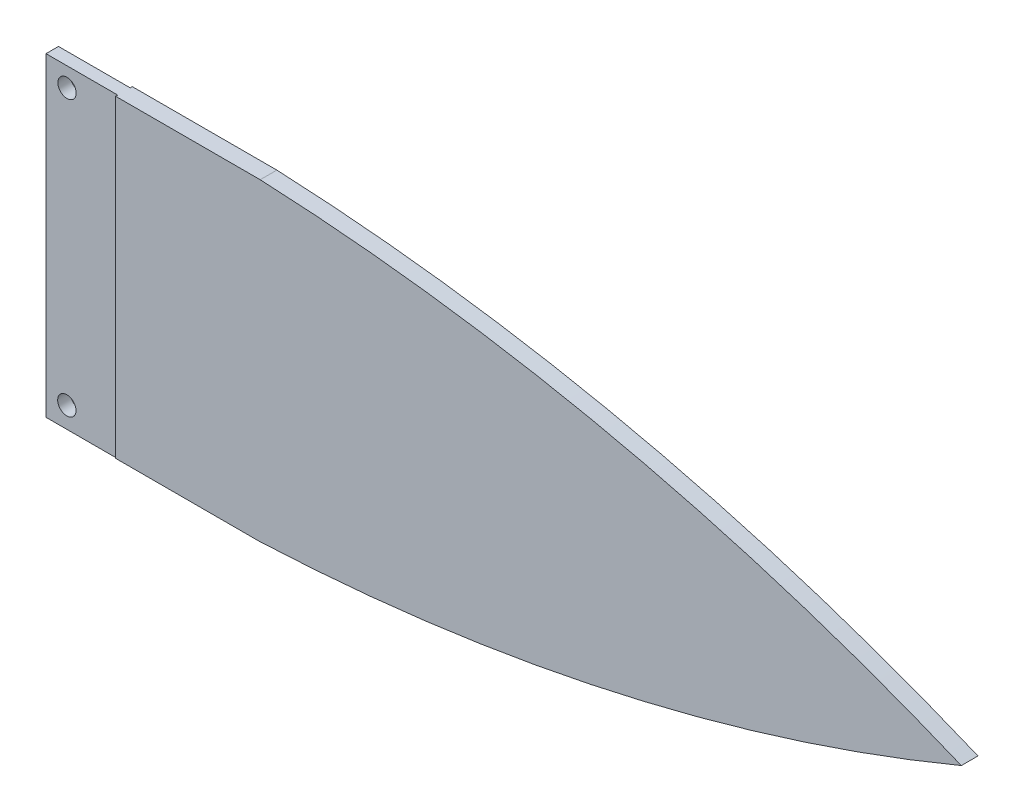
SolidWorks part; units mm, degrees
ref_plane "前基準面" through (0, 0, 0) normal (0, 0, 1) x (1, 0, 0)
ref_plane "上基準面" through (0, 0, 0) normal (0, 1, 0) x (1, 0, 0)
ref_plane "右基準面" through (0, 0, 0) normal (1, 0, 0) x (0, 0, -1)
sketch "草圖1" plane through (0, 0, 0) normal (0, 0, 1) x (1, 0, 0)
  line L0 (-6.5784, -18.2648) -> (-6.5784, 19.7352) construction
  line L4 (0.8982, 19.7352) -> (0.8982, -18.2648)
  line L13 (-4.1018, 17.2352) -> (-9.1018, 17.2352) construction
  line L14 (-4.1018, -15.7648) -> (-9.1018, -15.7648) construction
  line L16 (-9.1018, 19.7352) -> (0.8982, 19.7352)
  line L17 (-9.1018, -18.2648) -> (0.8982, -18.2648)
  line L18 (-9.1018, 19.7352) -> (-9.1018, -18.2648)
  circle A0 centre (-6.6018, -15.7648) radius 1.1
  circle A1 centre (-6.5784, 17.2352) radius 1.1
  dimension "D7" = 2.2
  dimension "D8" = 2.2
  dimension "D1" = 38
  dimension "D2" = 10
extrude "填料-伸長1" add sketch "草圖1" along normal blind 0.75 and the other way blind 0.75
ref_plane "平面1" through (-0.5, 0, 0) normal (1, 0, 0) x (0, 0, -1)
sketch "草圖3" plane through (-0.5, 0, 0) normal (1, 0, 0) x (0, 0, -1)
  line L0 (0, 19.7352) -> (0, -18.3016) construction
  line L1 (-10, 19.7352) -> (10, 19.7352)
  line L2 (-10, 19.7352) -> (-10, -18.3016)
  line L3 (-10, -18.3016) -> (10, -18.3016)
  line L4 (10, 19.7352) -> (10, -18.3016)
  line L5 (-0.75, -18.2648) -> (-0.75, 19.7352) construction
  line L6 (0.75, 19.7352) -> (-0.75, 19.7352) construction
  dimension "D1" = 0.75
  dimension "D2" = 10
  dimension "D3" = 0
extrude "填料-伸長2" add sketch "草圖3" along normal blind 1.5
sketch "草圖4" plane through (0, 0, 0) normal (0, 0, 1) x (1, 0, 0)
  line L2 (1, 19.7352) -> (1, -18.2989)
  line L5 (101, 0.7182) -> (1, 0.7182) construction
  arc A0 (1, 19.7352) -> (101, 0.7182) centre (5.8112, -227.3957) cw
  arc A1 (1, -18.2989) -> (101, 0.7182) centre (5.8112, 228.8321) ccw
  dimension "D1" = 100
extrude "填料-伸長3" add sketch "草圖4" along normal blind 1 and the other way blind 1
ref_plane "平面2" through (0, 19.7352, 0) normal (0, 1, 0) x (1, 0, 0)
ref_plane "平面3" through (0, 0, 10) normal (0, 0, 1) x (1, 0, 0)
ref_plane "平面4" through (0, 19.7352, 0) normal (0, 1, 0) x (1, 0, 0)
ref_plane "平面5" through (0, 19.7352, 0) normal (0, 1, 0) x (1, 0, 0)
sketch "草圖10" plane through (0, 19.7352, 0) normal (0, 1, 0) x (1, 0, 0)
  line L0 (-22.4534, -10) -> (22.4534, -10) construction
  line L1 (-9.7542, 10.5434) -> (102.7429, 10.5434)
  line L2 (-9.7542, 10.5434) -> (-9.7542, -10)
  line L3 (-9.7542, -10) -> (102.7429, -10)
  line L4 (102.7429, 10.5434) -> (102.7429, -10)
extrude "除料-伸長4" cut sketch "草圖10" against normal blind 0.2 and the other way blind 0.2
ref_plane "平面6" through (0, -18.3016, 0) normal (0, -1, 0) x (-1, 0, 0)
sketch "草圖11" plane through (0, -18.3016, 0) normal (0, -1, 0) x (-1, 0, 0)
  line L0 (-22.4534, -10) -> (22.4534, -10) construction
  line L1 (0.716, -10) -> (-103.7986, -10)
  line L2 (0.716, -10) -> (0.716, 11.6577)
  line L3 (0.716, 11.6577) -> (-103.7986, 11.6577)
  line L4 (-103.7986, -10) -> (-103.7986, 11.6577)
extrude "除料-伸長5" cut sketch "草圖11" against normal blind 0.2 and the other way blind 0.2
sketch "草圖12" plane through (0, 19.7352, 0) normal (0, 1, 0) x (1, 0, 0)
  line L1 (-0.5, -10) -> (1, -10)
  line L2 (-0.5, -10) -> (-0.5, -1)
  line L3 (-0.5, -1) -> (1, -1)
  line L4 (1, -10) -> (1, -1)
  line L5 (-0.5, 10) -> (1, 10)
  line L6 (-0.5, 10) -> (-0.5, 1)
  line L7 (-0.5, 1) -> (1, 1)
  line L8 (1, 10) -> (1, 1)
extrude "除料-伸長6" cut sketch "草圖12" against normal blind 39
